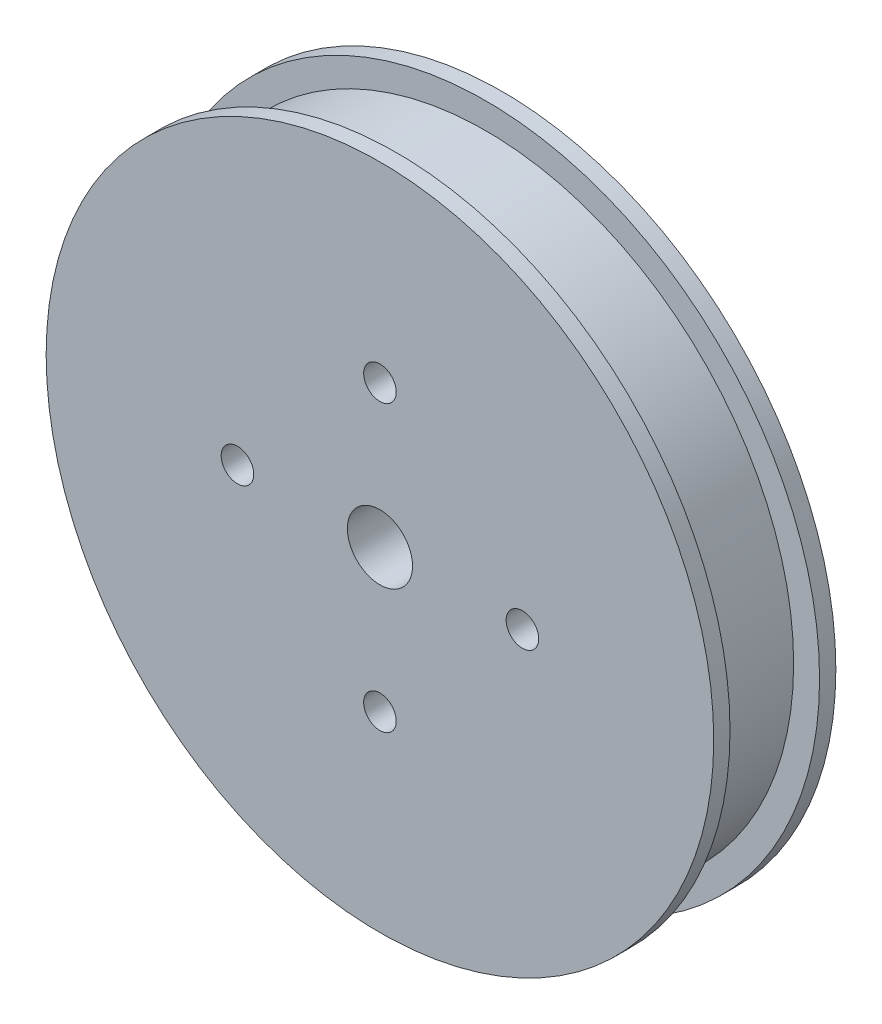
SolidWorks part; units mm, degrees
material "6061 Alloy"
ref_plane "Front" through (0, 0, 0) normal (0, 0, 1) x (1, 0, 0)
ref_plane "Top" through (0, 0, 0) normal (0, 1, 0) x (1, 0, 0)
ref_plane "Right" through (0, 0, 0) normal (1, 0, 0) x (0, 0, -1)
sketch "草图1" plane through (0, 0, 0) normal (0, 0, 1) x (1, 0, 0)
  circle A0 centre (0, 0) radius 41
  circle A1 centre (0, 0) radius 4
  circle A2 centre (0, 0) radius 17.5 construction
  circle A3 centre (-17.5, 0) radius 2
  circle A4 centre (0, 17.5) radius 2
  circle A5 centre (17.5, 0) radius 2
  circle A6 centre (0, -17.5) radius 2
  point P16 (0, 0)
  dimension "D1" = 82
  dimension "D2" = 8
  dimension "D3" = 35
  dimension "D4" = 4
  dimension "D5" = 4
extrude "凸台-拉伸1" add sketch "草图1" along normal blind 15
sketch "草图3" plane through (0, 0, 15) normal (0, 0, 1) x (1, 0, 0)
  circle A0 centre (0, 0) radius 37.815
  circle A1 centre (0, 0) radius 41
  dimension "D1" = 75.63
extrude "切除-拉伸1" cut sketch "草图3" against normal blind 11 from offset 2 offset against normal yes
